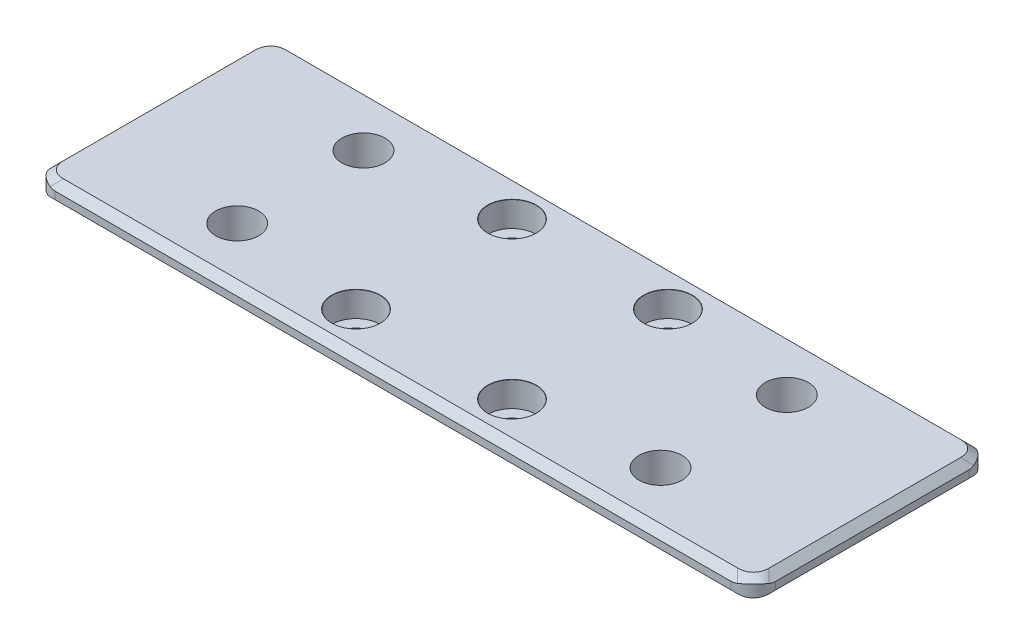
SolidWorks part; units mm, degrees
ref_plane "Front Plane" through (0, 0, 0) normal (0, 0, 1) x (1, 0, 0)
ref_plane "Top Plane" through (0, 0, 0) normal (0, 1, 0) x (1, 0, 0)
ref_plane "Right Plane" through (0, 0, 0) normal (1, 0, 0) x (0, 0, -1)
sketch "Sketch1" plane through (0, 0, 0) normal (0, 1, 0) x (1, 0, 0)
  line L1 (-48.5, 16) -> (48.5, 16)
  line L2 (-48.5, 16) -> (-48.5, -16)
  line L3 (-48.5, -16) -> (48.5, -16)
  line L4 (48.5, 16) -> (48.5, -16)
  line L5 (-48.5, 16) -> (48.5, -16) construction
  line L6 (-48.5, -16) -> (48.5, 16) construction
  point P0 (0, 0)
  dimension "D1" = 32
  dimension "D2" = 97
extrude "Boss-Extrude1" add sketch "Sketch1" along normal blind 5
sketch "Sketch2" plane through (0, 5, 0) normal (0, 1, 0) x (1, 0, 0)
  line L1 (-28.5, -8.5) -> (28.5, -8.5) construction
  line L2 (-28.5, -8.5) -> (-28.5, 8.5) construction
  line L3 (-28.5, 8.5) -> (28.5, 8.5) construction
  line L4 (28.5, -8.5) -> (28.5, 8.5) construction
  line L5 (-28.5, -8.5) -> (28.5, 8.5) construction
  line L6 (-28.5, 8.5) -> (28.5, -8.5) construction
  point P0 (0, 0)
  dimension "D1" = 17
  dimension "D2" = 57
hole_wizard "Hole1" positions "Sketch3" profile "Sketch4" legacy
sketch "Sketch3" plane through (0, 5, 0) normal (0, 1, 0) x (1, 0, 0)
  point P0 (-28.5, 8.5)
  point P3 (-28.5, -8.5)
  point P6 (28.5, -8.5)
  point P9 (28.5, 8.5)
sketch "Sketch4" plane through (-28.5, 5, -8.5) normal (1, 0, 0) x (0, 0, 1)
  line L0 (0, 0) -> (0, 6)
  line L1 (0, 6) -> (2.9, 6)
  line L2 (2.9, 6) -> (2.9, 0)
  line L3 (2.9, 0) -> (0, 0)
  line L4 (0, 110) -> (0, -10) construction
  dimension "Diameter" = 5.8
  dimension "Depth" = 6
chamfer "Chamfer1" distance 1 angle 45 4 edges at (0, 5, 16) (48.5, 5, 0) (0, 5, -16) (-48.5, 5, 0)
chamfer "Chamfer2" distance 3 angle 45 4 edges at (48.5, 0, 0) (0, 0, 16) (-48.5, 0, 0) (0, 0, -16)
fillet "Fillet1" radius 3 12 edges at (-48.5, 3.5, 16) (-48.5, 3.5, -16) (48.5, 3.5, -16) (48.5, 3.5, 16) (47, 1.5, 14.5) (47, 1.5, -14.5) (-47, 1.5, -14.5) (-47, 1.5, 14.5) (-48, 4.5, -15.5) (48, 4.5, 15.5) (-48, 4.5, 15.5) (48, 4.5, -15.5)
sketch "Sketch5" plane through (0, 5, 0) normal (0, 1, 0) x (1, 0, 0)
  line L0 (-10.5, 10.5) -> (10.5, 10.5) construction
  line L6 (10.5, 10.5) -> (10.5, -10.5) construction
  line L7 (-15, -16) -> (15, -16) construction
  line L8 (-15, -16) -> (-15, 16) construction
  line L9 (-15, 16) -> (15, 16) construction
  line L10 (15, -16) -> (15, 16) construction
  line L11 (-15, -16) -> (15, 16) construction
  line L12 (-15, 16) -> (15, -16) construction
  line L13 (10.5, -10.5) -> (-10.5, -10.5) construction
  line L14 (-10.5, -10.5) -> (-10.5, 10.5) construction
  line L15 (-45.5, 16) -> (45.5, 16) construction
  line L16 (45.5, -16) -> (-45.5, -16) construction
  circle A0 centre (-10.5, 10.5) radius 1.5 construction
  circle A1 centre (10.5, 10.5) radius 1.5 construction
  circle A2 centre (10.5, -10.5) radius 1.5 construction
  circle A3 centre (-10.5, -10.5) radius 1.5 construction
  point P0 (0, 0)
  point P8 (0, 0)
  point P15 (-7.8226, -12.023)
  point P16 (-6.8534, -12.4193)
  point P17 (0, 0)
  point P20 (-17.3185, -11.8879)
  point P23 (0, 0)
  dimension "D1" = 3
  dimension "D2" = 4
  dimension "D5" = 18
  dimension "D6" = 18
  dimension "D7" = 3
  dimension "D3" = 30
hole_wizard "CBORE for M3 Hex Socket Head Cap Screw1" positions "Sketch6" profile "Sketch7" counterbore size "M3" standard "ISO" end condition through all
sketch "Sketch6" plane through (0, 5, 0) normal (0, 1, 0) x (1, 0, 0)
  point P0 (10.5, 10.5)
  point P3 (-10.5, 10.5)
  point P6 (10.5, -10.5)
  point P9 (-10.5, -10.5)
sketch "Sketch7" plane through (10.5, 5, -10.5) normal (1, 0, 0) x (0, 0, 1)
  line L0 (0, 0) -> (0, 5)
  line L1 (0, 5) -> (1.7, 5)
  line L3 (1.7, 5) -> (1.7, 3.4)
  line L4 (3.25, 3.4) -> (1.7, 3.4)
  line L5 (3.25, 3.4) -> (3.25, 0.025)
  line L6 (3.25, 0.025) -> (3.275, 0)
  line L7 (3.275, 0) -> (0, 0)
  line L8 (-3.25, 0.025) -> (-3.275, 0) construction
  line L11 (0, -6.35) -> (0, 107.95) construction
  dimension "Thru Hole Dia." = 3.4
  dimension "Thru Hole Depth" = 5
  dimension "C'Bore Dia." = 6.5
  dimension "C'Bore Depth" = 3.4
  dimension "Near C'Sink Dia." = 6.55
  dimension "Near C'Sink Angle" = 90
